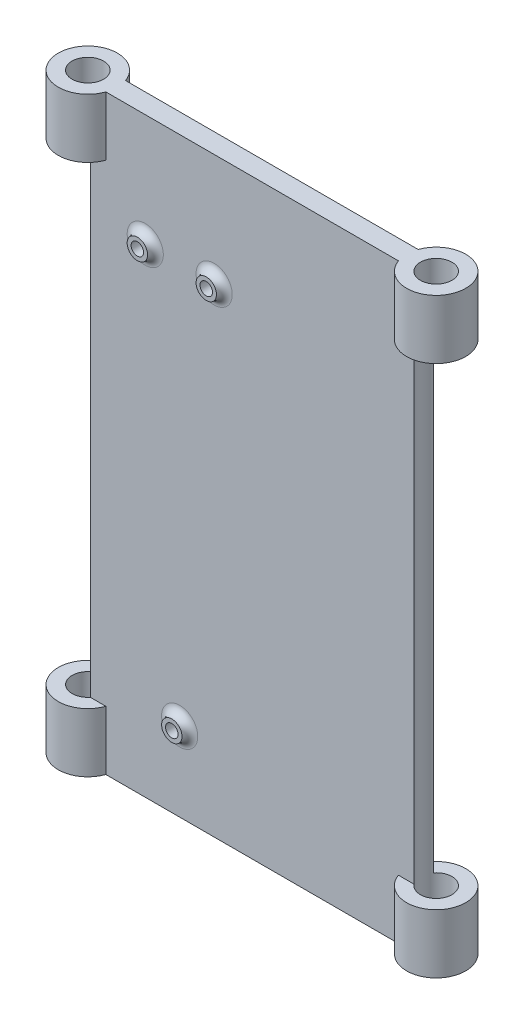
SolidWorks part; units mm, degrees
ref_plane "정면" through (0, 0, 0) normal (0, 0, 1) x (1, 0, 0)
ref_plane "윗면" through (0, 0, 0) normal (0, 1, 0) x (1, 0, 0)
ref_plane "우측면" through (0, 0, 0) normal (1, 0, 0) x (0, 0, -1)
sketch "스케치1" plane through (0, 0, 0) normal (0, 0, 1) x (1, 0, 0)
  line L1 (0, 0) -> (88.39, 0)
  line L2 (0, 0) -> (0, 150)
  line L3 (0, 150) -> (88.39, 150)
  line L4 (88.39, 0) -> (88.39, 150)
  dimension "D1" = 88.39
  dimension "D2" = 150
extrude "보스-돌출1" add sketch "스케치1" along normal blind 5
sketch "스케치2" plane through (0, 150, 0) normal (0, 1, 0) x (1, 0, 0)
  line L0 (88.39, -5) -> (88.39, 0) construction
  line L1 (0, -5) -> (0, 0) construction
  circle A0 centre (88.39, -2.5) radius 7.5
  circle A1 centre (0, -2.5) radius 7.5
  dimension "D1" = 15
  dimension "D2" = 15
extrude "보스-돌출2" add sketch "스케치2" against normal blind 15
hole_wizard "구멍1" positions "스케치3" profile "스케치4" legacy end condition through all
sketch "스케치3" plane through (0, 150, 0) normal (0, 1, 0) x (1, 0, 0)
  point P0 (0, -2.5)
  point P3 (88.39, -2.5)
sketch "스케치4" plane through (0, 150, 2.5) normal (1, 0, 0) x (0, 0, 1)
  line L0 (0, 0) -> (0, 150)
  line L1 (0, 150) -> (4, 150)
  line L2 (4, 150) -> (4, 0)
  line L3 (4, 0) -> (0, 0)
  line L4 (0, 110) -> (0, -10) construction
  dimension "지름" = 8
  dimension "깊이" = 150
sketch "스케치6" plane through (0, 0, 0) normal (0, 0, -1) x (-1, 0, 0)
  line L0 (-44.195, 150) -> (-44.195, -8.7542) construction
  line L1 (-81.3189, 150) -> (-7.0711, 150) construction
sketch "스케치7" plane through (0, 0, 0) normal (0, -1, 0) x (1, 0, 0)
  line L0 (81.3189, 0) -> (85.2675, 0)
  line L1 (81.3189, 5) -> (85.2675, 5)
  line L2 (85.2675, 5) -> (3.1225, 5)
  line L3 (3.1225, 0) -> (85.2675, 0)
  line L6 (3.1225, 5) -> (7.0711, 5)
  line L7 (3.1225, 0) -> (7.0711, 0)
  arc A2 (3.1225, 0) -> (3.1225, 5) centre (0, 2.5) ccw
  arc A3 (85.2675, 5) -> (85.2675, 0) centre (88.39, 2.5) ccw
  arc A4 (3.1225, 0) -> (3.1225, 5) centre (0, 2.5) ccw
  arc A5 (85.2675, 5) -> (85.2675, 0) centre (88.39, 2.5) ccw
  arc A6 (7.0711, 5) -> (7.0711, 0) centre (0, 2.5) ccw construction
  arc A8 (7.0711, 5) -> (7.0711, 0) centre (0, 2.5) ccw
  arc A10 (81.3189, 0) -> (81.3189, 5) centre (88.39, 2.5) ccw construction
  arc A12 (81.3189, 0) -> (81.3189, 5) centre (88.39, 2.5) ccw
  dimension "D1" = 0
extrude "보스-돌출3" add sketch "스케치7" against normal blind 15
sketch "스케치8" plane through (0, 15, 0) normal (0, 1, 0) x (1, 0, 0)
  circle A0 centre (0, -2.5) radius 4 construction
  circle A1 centre (88.39, -2.5) radius 4 construction
  circle A2 centre (0, -2.5) radius 4
  circle A3 centre (88.39, -2.5) radius 4
extrude "컷-돌출1" cut sketch "스케치8" against normal through all
hole_wizard "구멍2" positions "스케치11" profile "스케치12" legacy end condition through all
sketch "스케치11" plane through (0, 0, 5) normal (0, 0, 1) x (1, 0, 0)
  line L0 (17.0711, 121.5) -> (34.5511, 121.5) construction
  line L4 (7.0711, 0) -> (81.3189, 0) construction
  line L6 (7.0711, 150) -> (7.0711, 135) construction
  point P0 (17.0711, 121.5)
  point P2 (34.5511, 121.5)
  point P4 (25.8111, 20)
  point P18 (25.8111, 121.5)
  dimension "D1" = 17.48
  dimension "D2" = 101.5
  dimension "D3" = 20
  dimension "D4" = 10
sketch "스케치12" plane through (17.0711, 121.5, 5) normal (1, 0, 0) x (0, -1, 0)
  line L0 (0, 0) -> (0, 10)
  line L1 (0, 10) -> (1.5875, 10)
  line L2 (1.5875, 10) -> (1.5875, 0)
  line L3 (1.5875, 0) -> (0, 0)
  line L4 (0, 110) -> (0, -10) construction
  dimension "지름" = 3.175
  dimension "깊이" = 10
sketch "스케치13" plane through (0, 0, 5) normal (0, 0, 1) x (1, 0, 0)
  circle A0 centre (17.0711, 121.5) radius 2.5875
  circle A1 centre (17.0711, 121.5) radius 1.5875 construction
  circle A2 centre (17.0711, 121.5) radius 1.5875
  circle A5 centre (34.5511, 121.5) radius 2.5875
  circle A6 centre (34.5511, 121.5) radius 2.5875
  circle A7 centre (25.8111, 20) radius 1.5875 construction
  circle A8 centre (25.8111, 20) radius 2.5875
  circle A9 centre (25.8111, 20) radius 2.5875
  circle A10 centre (34.5511, 121.5) radius 1.5875 construction
  circle A11 centre (25.8111, 20) radius 1.5875
  circle A12 centre (34.5511, 121.5) radius 1.5875
  dimension "D1" = 1
  dimension "D2" = 1
  dimension "D3" = 1
extrude "보스-돌출5" add sketch "스케치13" along normal blind 2
fillet "필렛2" radius 2 3 edges at (14.4836, 121.5, 5) (23.2236, 20, 5) (31.9636, 121.5, 5)
